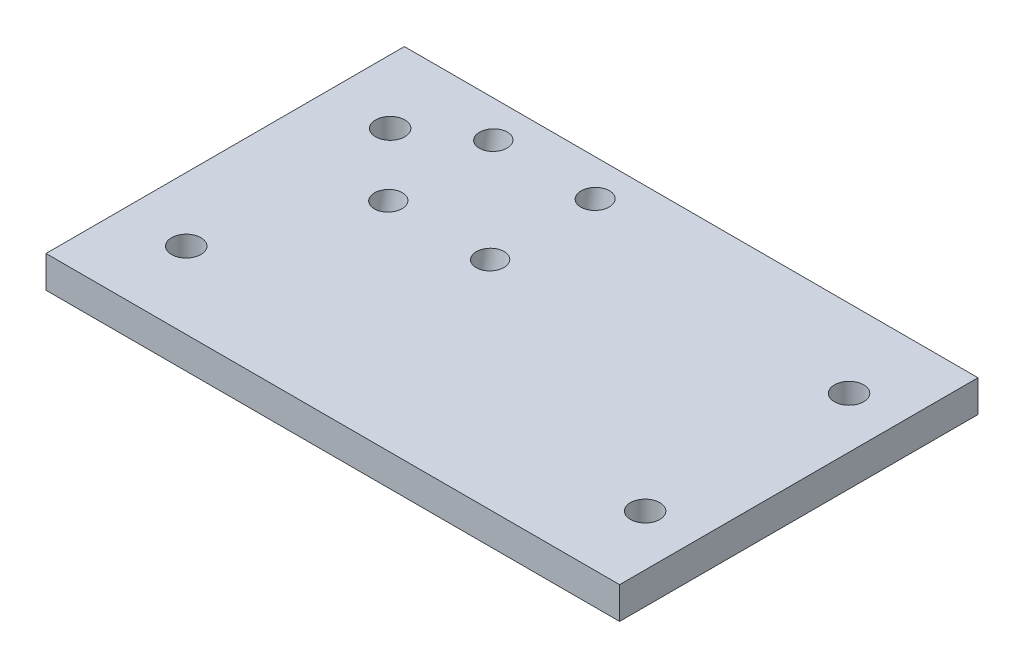
SolidWorks part; units mm, degrees
ref_plane "Front" through (0, 0, 0) normal (0, 0, 1) x (1, 0, 0)
ref_plane "Top" through (0, 0, 0) normal (0, 1, 0) x (1, 0, 0)
ref_plane "Right" through (0, 0, 0) normal (1, 0, 0) x (0, 0, -1)
sketch "Sketch1" plane through (0, 0, 0) normal (0, 1, 0) x (1, 0, 0)
  line L1 (0, 0) -> (90, 0)
  line L2 (0, 0) -> (0, 56.23)
  line L3 (0, 56.23) -> (90, 56.23)
  line L4 (90, 0) -> (90, 56.23)
  dimension "D1" = 90
  dimension "D2" = 56.23
extrude "Boss-Extrude1" add sketch "Sketch1" along normal blind 5
sketch "Sketch2" plane through (0, 5, 0) normal (0, 1, 0) x (1, 0, 0)
  circle A0 centre (82, 12) radius 2.3
  circle A1 centre (10, 12) radius 2.3
extrude "Cut-Extrude1" cut sketch "Sketch2" against normal blind 15
sketch "Sketch4" plane through (0, 5, 0) normal (0, 1, 0) x (1, 0, 0)
  circle A0 centre (39.2121, 27.5705) radius 2.204
  circle A1 centre (23.8176, 32.2728) radius 4.0674
  circle A2 centre (43.572, 44.174) radius 17.6111
  circle A3 centre (28.1775, 48.8763) radius 2.2
ref_plane "Plane1" through (0, 15.35, -2.9837) normal (0, 0.9816, -0.1908) x (-1, 0, 0)
sketch "Sketch7" plane through (0, 5, 0) normal (0, 1, 0) x (1, 0, 0)
  circle A0 centre (82, 44) radius 2.3
  circle A1 centre (10, 44) radius 2.3
extrude "Cut-Extrude3" cut sketch "Sketch7" against normal blind 45
sketch "Sketch8" plane through (0, 5, 0) normal (0, 1, 0) x (1, 0, 0)
  circle A0 centre (35.6711, 34.0145) radius 2.2
  circle A1 centre (19.6912, 34.0145) radius 2.2
  circle A2 centre (19.6912, 50.492) radius 2.2
  circle A3 centre (35.6711, 50.492) radius 2.2
  circle A4 centre (19.6912, 34.0145) radius 2.2
  circle A5 centre (35.6711, 34.0145) radius 2.2
  circle A6 centre (35.6711, 50.492) radius 2.2
  circle A7 centre (19.6912, 50.492) radius 2.2
sketch "Sketch10" plane through (0, 15.35, -2.9837) normal (0, 0.9816, -0.1908) x (-1, 0, 0)
  circle A0 centre (-35.6711, -32.4355) radius 2.1596
  circle A1 centre (-19.6912, -32.4355) radius 2.1596
  circle A2 centre (-19.6912, -48.6102) radius 2.1596
  circle A3 centre (-35.6711, -48.6102) radius 2.2
extrude "Cut-Extrude4" cut sketch "Sketch10" against normal blind 10
